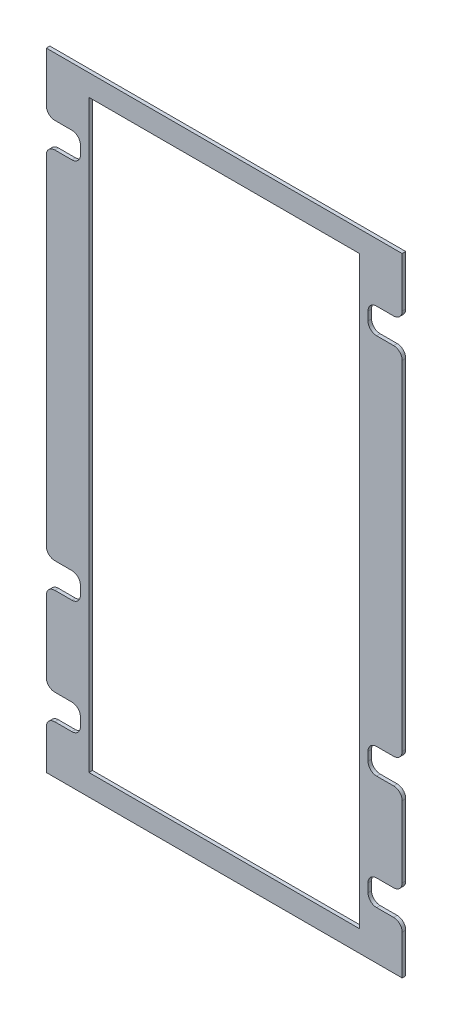
SolidWorks part; units mm, degrees
ref_plane "Front Plane" through (0, 0, 0) normal (0, 0, 1) x (1, 0, 0)
ref_plane "Top Plane" through (0, 0, 0) normal (0, 1, 0) x (1, 0, 0)
ref_plane "Right Plane" through (0, 0, 0) normal (1, 0, 0) x (0, 0, -1)
sketch "Sketch1" plane through (0, 0, 0) normal (0, 0, 1) x (1, 0, 0)
  line L1 (-158.75, 279.8534) -> (158.75, 279.8534)
  line L2 (-158.75, 279.8534) -> (-158.75, -279.8534)
  line L3 (-158.75, -279.8534) -> (158.75, -279.8534)
  line L4 (158.75, 279.8534) -> (158.75, -279.8534)
  line L5 (-158.75, 279.8534) -> (158.75, -279.8534) construction
  line L6 (-158.75, -279.8534) -> (158.75, 279.8534) construction
  point P0 (0, 0)
  dimension "D1" = 317.5
  dimension "D2" = 559.7068
extrude "Boss-Extrude1" add sketch "Sketch1" along normal blind 3.175
sketch "Sketch2" plane through (0, 0, 3.175) normal (0, 0, 1) x (1, 0, 0)
  circle A0 centre (-137.3162, -225.4237) radius 3.556 construction
  circle A1 centre (-137.3162, -123.8288) radius 3.3782 construction
  circle A2 centre (-137.3162, -225.4237) radius 3.556
  circle A3 centre (-137.3162, -123.8288) radius 3.3782
sketch "Sketch3" plane through (0, 0, 3.175) normal (0, 0, 1) x (1, 0, 0)
  circle A0 centre (-137.3162, 216.3559) radius 3.3782 construction
  circle A1 centre (-137.3162, 216.3559) radius 3.3782
sketch "Sketch4" plane through (0, 0, 0) normal (0, 0, -1) x (-1, 0, 0)
  circle A0 centre (137.3162, 216.3559) radius 7.1438
  circle A1 centre (137.3162, -123.8288) radius 7.1438
  circle A2 centre (137.3162, -225.4237) radius 7.1438
  dimension "D1" = 14.2875
sketch "Sketch5" plane through (0, 0, 0) normal (0, 0, -1) x (-1, 0, 0)
  line L0 (-158.75, -279.8534) -> (-158.75, 279.8534) construction
  line L1 (-120.65, 260.8034) -> (120.65, 260.8034)
  line L2 (-120.65, 260.8034) -> (-120.65, -260.8034)
  line L3 (-120.65, -260.8034) -> (120.65, -260.8034)
  line L4 (120.65, 260.8034) -> (120.65, -260.8034)
  line L5 (-120.65, 260.8034) -> (120.65, -260.8034) construction
  line L6 (-120.65, -260.8034) -> (120.65, 260.8034) construction
  line L7 (-158.75, 279.8534) -> (158.75, 279.8534) construction
  line L8 (158.75, 279.8534) -> (158.75, -279.8534) construction
  line L9 (158.75, 227.7859) -> (128.27, 227.7859)
  line L10 (158.75, 227.7859) -> (158.75, 204.9259)
  line L11 (158.75, 204.9259) -> (128.27, 204.9259)
  line L12 (128.27, 227.7859) -> (128.27, 204.9259)
  line L14 (158.75, -236.8537) -> (128.27, -236.8537)
  line L15 (158.75, -236.8537) -> (158.75, -213.9937)
  line L16 (158.75, -213.9937) -> (128.27, -213.9937)
  line L17 (128.27, -236.8537) -> (128.27, -213.9937)
  line L18 (158.75, -135.2588) -> (128.27, -135.2588)
  line L19 (158.75, -135.2588) -> (158.75, -112.3988)
  line L20 (158.75, -112.3988) -> (128.27, -112.3988)
  line L21 (128.27, -135.2588) -> (128.27, -112.3988)
  point P0 (0, 0)
  line M17 (158.75, -279.8534) -> (158.75, 279.8534)
  dimension "D1" = 38.1
  dimension "D2" = 19.05
  dimension "D3" = 30.48
  dimension "D4" = 22.86
  dimension "D5" = 11.43
  dimension "D6" = 22.86
  dimension "D7" = 11.43
  dimension "D8" = 22.86
  dimension "D9" = 11.43
extrude "Cut-Extrude1" cut sketch "Sketch5" against normal through all contours L9 L12 L11 M17 | L21 L18 L20 M17 | L17 L14 L16 M17 region at (-143.51, 216.3559, 0) region at (-143.51, -225.4237, 0) region at (-143.51, -123.8288, 0)
mirror "Mirror1" about plane through (0, 0, 0) normal (1, 0, 0) of "Cut-Extrude1"
fillet "Fillet1" radius 7.62 24 edges at (-158.75, -236.8537, 1.5875) (-128.27, -236.8537, 1.5875) (-128.27, -213.9937, 1.5875) (-158.75, -213.9937, 1.5875) (-158.75, -135.2588, 1.5875) (-128.27, -135.2588, 1.5875) (-128.27, -112.3988, 1.5875) (-158.75, -112.3988, 1.5875) (-158.75, 204.9259, 1.5875) (-128.27, 204.9259, 1.5875) (-128.27, 227.7859, 1.5875) (-158.75, 227.7859, 1.5875) (158.75, 227.7859, 1.5875) (128.27, 227.7859, 1.5875) (128.27, 204.9259, 1.5875) (158.75, 204.9259, 1.5875) (158.75, -112.3988, 1.5875) (128.27, -112.3988, 1.5875) (128.27, -135.2588, 1.5875) (158.75, -135.2588, 1.5875) (158.75, -213.9937, 1.5875) (128.27, -213.9937, 1.5875) (128.27, -236.8537, 1.5875) (158.75, -236.8537, 1.5875)
extrude "Cut-Extrude2" cut sketch "Sketch5<3>" against normal through all contours L4 L1 L2 L3 region at (0, 0, 0)
sketch "Sketch5<3>" plane through (0, 0, 0) normal (0, 0, -1) x (-1, 0, 0) same geometry as "Sketch5"
